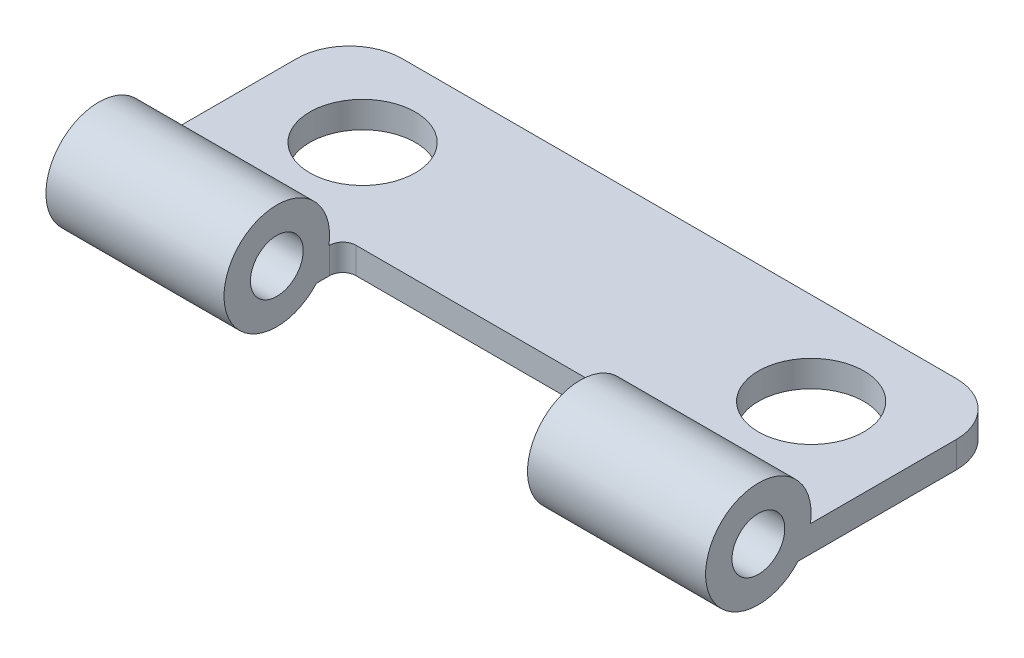
SolidWorks part; units mm, degrees
ref_plane "前视基准面" through (0, 0, 0) normal (0, 0, 1) x (1, 0, 0)
ref_plane "上视基准面" through (0, 0, 0) normal (0, 1, 0) x (1, 0, 0)
ref_plane "右视基准面" through (0, 0, 0) normal (1, 0, 0) x (0, 0, -1)
other "Configuration Table"
sketch "草图1" plane through (0, 0, 0) normal (0, 1, 0) x (1, 0, 0)
  line L0 (-5.75, 0) -> (5.75, 0) construction
  line L1 (-5.75, 0) -> (-5.75, 1)
  line L2 (-5.75, 1) -> (-12.5, 1) construction
  line L3 (-12.5, 1) -> (-12.5, 8)
  line L4 (-12.5, 8) -> (12.5, 8)
  line L5 (12.5, 8) -> (12.5, 1)
  line L6 (12.5, 1) -> (5.75, 1) construction
  line L7 (5.75, 1) -> (5.75, 0)
  line L8 (0, 0) -> (0, 8) construction
  line L9 (-12.5, 1) -> (-12.5, 0)
  line L10 (-12.5, 0) -> (-5.75, 0)
  line L11 (5.75, 0) -> (12.5, 0)
  line L12 (12.5, 0) -> (12.5, 1)
  line L13 (-5.75, 1) -> (5.75, 1)
  line L14 (-12.5, 4.5) -> (12.5, 4.5) construction
  circle A0 centre (-8.5, 4.5) radius 2
  circle A1 centre (8.5, 4.5) radius 2
  point P2 (0, 0)
  point P20 (-7.5852, 4.5)
  dimension "D5" = 4
  dimension "D1" = 25
  dimension "D2" = 7
  dimension "D3" = 1
  dimension "D4" = 11.5
  dimension "D6" = 17
extrude "凸台-拉伸1" add sketch "草图1" along normal blind 1
fillet "圆角1" radius 2 2 edges at (-12.5, 0.5, -8) (12.5, 0.5, -8)
fillet "圆角2" radius 0.5 2 edges at (5.75, 0.5, -1) (-5.75, 0.5, -1)
sketch "草图2" plane through (0, 0, 0) normal (1, 0, 0) x (0, 0, -1)
  line L0 (1, 1) -> (1, 0) construction
  circle A0 centre (-1.5, 1.3229) radius 1
  circle A1 centre (-1.5, 1.3229) radius 2
  point P3 (-1.5939, 1.208)
  point P7 (-1.5, 1.7921)
  dimension "D1" = 4
  dimension "D2" = 2
  dimension "D3" = 2.5
extrude "凸台-拉伸2" add sketch "草图2" against normal up to surface (12.5 mm away) from surface up to face at (-12.5, 0.5, -3) starting at face at (-5.75, 0.5, -0.25)
extrude "凸台-拉伸3" add sketch "草图2<3>" along normal up to surface (12.5 mm away) from surface up to face at (12.5, 0.5, -3) starting at face at (5.75, 0.5, -0.25)
sketch "草图2<3>" plane through (0, 0, 0) normal (1, 0, 0) x (0, 0, -1) same geometry as "草图2"
